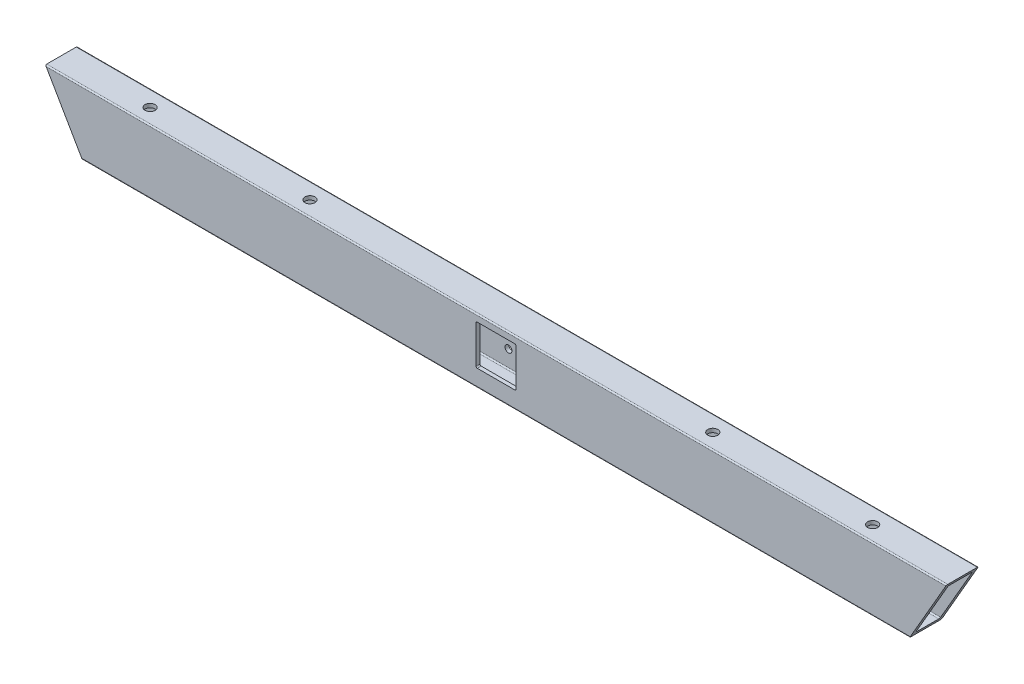
SolidWorks part; units mm, degrees
ref_plane "Front Plane" through (0, 0, 0) normal (0, 0, 1) x (1, 0, 0)
ref_plane "Top Plane" through (0, 0, 0) normal (0, 1, 0) x (1, 0, 0)
ref_plane "Right Plane" through (0, 0, 0) normal (1, 0, 0) x (0, 0, -1)
sketch "Sketch2" plane through (0, 0, 0) normal (0, 0, 1) x (1, 0, 0)
  line L0 (-328.5706, -25.4) -> (-357.9, 25.4)
  line L1 (-357.9, 25.4) -> (357.9, 25.4)
  line L3 (-328.5706, -25.4) -> (328.5706, -25.4)
  line L5 (0, 25.4) -> (0, -25.4) construction
  line L8 (328.5706, -25.4) -> (357.9, 25.4)
  point P0 (0, 0)
  point P4 (0, 0)
  point P8 (0, 25.4)
  dimension "D1" = 50.8
  dimension "D2" = 60
  dimension "D3" = 715.8
extrude "Boss-Extrude1" add sketch "Sketch2" along normal mid plane 25.4 contours L1 L8 L3 L0
sketch "Sketch3" plane through (0, 0, 0) normal (1, 0, 0) x (0, 0, -1)
  line L12 (9.652, -22.352) -> (9.652, 22.352)
  line L13 (-9.652, -22.352) -> (9.652, -22.352)
  line L14 (-9.652, 22.352) -> (-9.652, -22.352)
  line L15 (9.652, 22.352) -> (-9.652, 22.352)
  line L16 (9.652, -22.352) -> (9.652, 22.352)
  line L17 (-9.652, -22.352) -> (9.652, -22.352)
  line L18 (-9.652, 22.352) -> (-9.652, -22.352)
  line L19 (9.652, 22.352) -> (-9.652, 22.352)
  dimension "D1" = 3.048
extrude "Cut-Extrude1" cut sketch "Sketch3" against normal through all and the other way through all contours L16 L19 L18 L17
fillet "Fillet1" radius 1 8 edges at (0, 22.352, 9.652) (0, 22.352, -9.652) (0, -22.352, -9.652) (0, -22.352, 9.652) (0, -25.4, -12.7) (0, -25.4, 12.7) (0, 25.4, -12.7) (0, 25.4, 12.7)
sketch "Sketch4" plane through (0, 0, -12.7) normal (0, 0, -1) x (-1, 0, 0)
  line L1 (7, 0) -> (7, 10)
  line L2 (-7, 0) -> (-7, 10)
  arc A0 (-7, 0) -> (7, 0) centre (0, 0) ccw
  arc A1 (7, 10) -> (-7, 10) centre (0, 10) ccw
  dimension "D1" = 14
  dimension "D2" = 10
extrude "Cut-Extrude2" cut sketch "Sketch4" against normal up to next
sketch "Sketch5" plane through (0, 0, 12.7) normal (0, 0, 1) x (1, 0, 0)
  line L0 (15.875, 4) -> (-15.875, 4) construction
  line L1 (14.875, -11.875) -> (-14.875, -11.875)
  line L2 (15.875, -10.875) -> (15.875, 18.875)
  line L3 (14.875, 19.875) -> (-14.875, 19.875)
  line L4 (-15.875, -10.875) -> (-15.875, 18.875)
  arc A0 (-14.875, -11.875) -> (-15.875, -10.875) centre (-14.875, -10.875) cw
  arc A1 (14.875, -11.875) -> (15.875, -10.875) centre (14.875, -10.875) ccw
  arc A2 (15.875, 18.875) -> (14.875, 19.875) centre (14.875, 18.875) ccw
  arc A3 (-14.875, 19.875) -> (-15.875, 18.875) centre (-14.875, 18.875) ccw
  point P1 (0, 19.875)
  dimension "D2" = 1
  dimension "D1" = 31.75
  dimension "D3" = 4
extrude "Cut-Extrude3" cut sketch "Sketch5" against normal up to next
hole_wizard "M5 Clearance Hole1" positions "Sketch12" profile "Sketch7" hole size "M5" standard "ANSI Metric" end condition up to next
sketch "Sketch12" plane through (0, 0, -9.652) normal (0, 0, 1) x (1, 0, 0)
  line L1 (12.5, 16.5) -> (12.5, -8.5) construction
  line L2 (12.5, -8.5) -> (-12.5, -8.5) construction
  circle A5 centre (-12.5, 16.5) radius 2.1 construction
  point P0 (-12.5, 16.5)
  point P2 (12.5, 16.5)
  point P4 (12.5, -8.5)
  point P6 (-12.5, -8.5)
  point P47 (0, -8.5)
  dimension "D1" = 25
  dimension "D2" = 25
sketch "Sketch7" plane through (-12.5, 16.5, -9.652) normal (1, 0, 0) x (0, -1, 0)
  line L0 (0, 0) -> (0, 3.048)
  line L1 (0, 3.048) -> (2.75, 3.048)
  line L2 (2.75, 3.048) -> (2.75, 0)
  line L5 (2.75, 0) -> (0, 0)
  line L11 (0, -6.35) -> (0, 107.95) construction
  dimension "Thru Hole Dia." = 5.5
  dimension "Thru Hole Depth" = 3.048
sketch "Sketch9" plane through (0, 0, -12.7) normal (0, 0, -1) x (-1, 0, 0)
  line L0 (-222.25, 0) -> (-215.9, 0) construction
  line L1 (-222.25, 7.1437) -> (-215.9, 7.1437)
  line L2 (-222.25, -7.1437) -> (-215.9, -7.1437)
  line L3 (0, 55) -> (0, -55) construction
  line L4 (222.25, 0) -> (215.9, 0) construction
  line L5 (222.25, 7.1437) -> (215.9, 7.1437)
  line L6 (222.25, -7.1437) -> (215.9, -7.1437)
  arc A0 (-222.25, 7.1437) -> (-222.25, -7.1437) centre (-222.25, 0) ccw
  arc A1 (-215.9, -7.1437) -> (-215.9, 7.1437) centre (-215.9, 0) ccw
  arc A2 (222.25, 7.1437) -> (222.25, -7.1437) centre (222.25, 0) cw
  arc A3 (215.9, -7.1437) -> (215.9, 7.1437) centre (215.9, 0) cw
  point P2 (-219.075, 0)
  point P12 (219.075, 0)
  dimension "D2" = 14.2875
  dimension "D1" = 6.35
  dimension "D3" = 215.9
extrude "Cut-Extrude4" cut sketch "Sketch9" against normal up to next
sketch "Sketch14" plane through (0, 25.4, 0) normal (0, 1, 0) x (1, 0, 0)
  line L0 (-159.9992, -0.5) -> (-286.9992, -0.5) construction
  line L1 (357.3226, -12.7) -> (-357.3226, -12.7) construction
  line L3 (159.9992, -0.5) -> (286.9992, -0.5) construction
  line L4 (0, 0) -> (0, 11.7) construction
  line L5 (357.9, 11.7) -> (-357.9, 11.7) construction
  circle A0 centre (-159.9992, -0.5) radius 4
  circle A2 centre (-286.9992, -0.5) radius 4
  circle A6 centre (286.9992, -0.5) radius 4
  circle A7 centre (159.9992, -0.5) radius 4
  dimension "D1" = 8
  dimension "D2" = 160
  dimension "D3" = 127
extrude "Cut-Extrude7" cut sketch "Sketch14" against normal up to next
mirror "Mirror1" [suppressed] of bodies 110 106
sketch "Sketch10" [suppressed] plane through (0, 0, 0) normal (1, 0, 0) x (0, 0, -1)
  line L0 (-12.7, -24.4) -> (-12.7, 24.4) construction
  line L1 (12.7, -25.4) -> (-12.7, -25.4)
  line L2 (12.7, -25.4) -> (12.7, 25.4)
  line L3 (12.7, 25.4) -> (-12.7, 25.4)
  line L4 (-12.7, -25.4) -> (-12.7, 25.4)
  line L5 (12.7, -25.4) -> (-12.7, 25.4) construction
  line L6 (12.7, 25.4) -> (-12.7, -25.4) construction
  line L7 (-11.7, 25.4) -> (11.7, 25.4) construction
  point P0 (0, 0)
extrude "Cut-Extrude5" [suppressed] cut sketch "Sketch10" against normal through all both and the other way through all
sketch "Sketch13" [suppressed] plane through (0, 0, -38.1) normal (0, 0, -1) x (-1, 0, 0)
  circle A0 centre (241.3, 0) radius 7.5
  dimension "D1" = 15
  dimension "D2" = 241.3
extrude "Cut-Extrude6" [suppressed] cut sketch "Sketch13" against normal up to next
